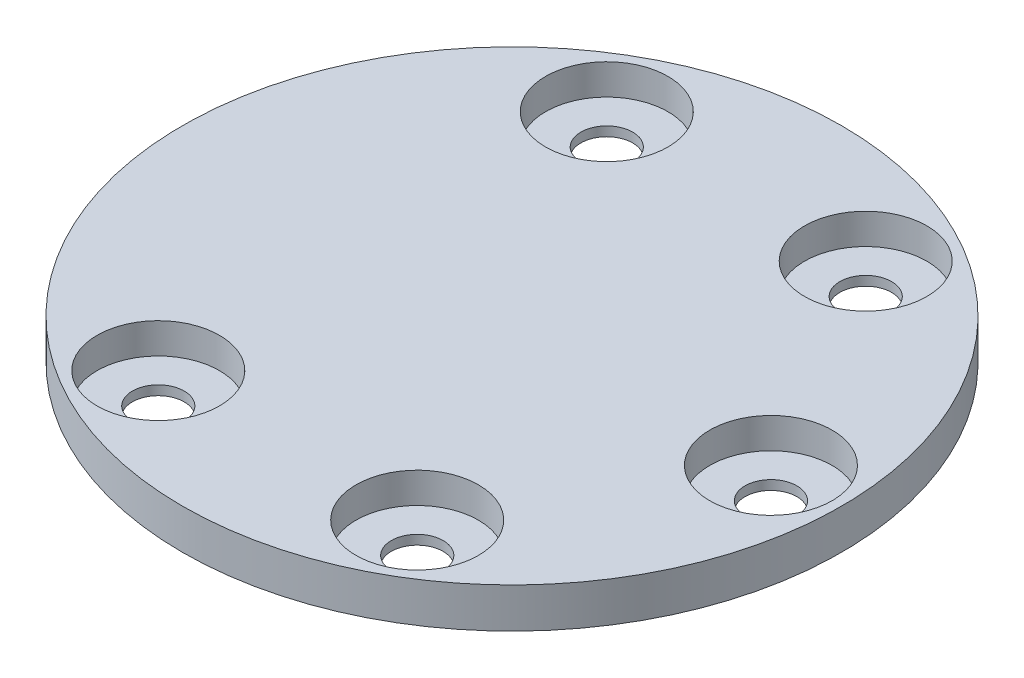
SolidWorks part; units mm, degrees
material "1060 Alloy"
ref_plane "Front Plane" through (0, 0, 0) normal (0, 0, 1) x (1, 0, 0)
ref_plane "Top Plane" through (0, 0, 0) normal (0, 1, 0) x (1, 0, 0)
ref_plane "Right Plane" through (0, 0, 0) normal (1, 0, 0) x (0, 0, -1)
sketch "Sketch1" plane through (0, 0, 0) normal (0, 1, 0) x (1, 0, 0)
  circle A0 centre (0, 0) radius 14
  dimension "D1" = 28
extrude "Boss-Extrude1" add sketch "Sketch1" along normal blind 1.7
sketch "Sketch3" plane through (0, 1.7, 0) normal (0, 1, 0) x (1, 0, 0)
  circle A0 centre (0, -10.25) radius 0.25
  circle A1 centre (0, 0) radius 9.8
  dimension "D1" = 0.5
  dimension "D2" = 10.25
  dimension "D3" = 19.6
sketch "Sketch4" plane through (0, 1.7, 0) normal (0, -1, 0) x (1, 0, 0)
  line L0 (0, 0) -> (13.2597, 13.2597) construction
  circle A0 centre (7.7782, 7.7782) radius 1
  dimension "D2" = 2
  dimension "D1" = 11
sketch "Sketch5" plane through (0, 1.7, 0) normal (0, 1, 0) x (1, 0, 0)
  circle A0 centre (0, 0) radius 11
  dimension "D1" = 22
hole_wizard "CBORE for M5 Hex Head Bolt1" positions "Sketch6" profile "Sketch7" counterbore size "M5" standard "ISO"
sketch "Sketch6" plane through (0, 1.7, 0) normal (0, 1, 0) x (1, 0, 0)
  point P0 (11, 0)
  dimension "D1" = 11
sketch "Sketch7" plane through (11, 1.7, 0) normal (1, 0, 0) x (0, 0, 1)
  line L0 (0, 0) -> (0, 5.6609)
  line L1 (0, 5.6609) -> (1.1, 5)
  line L2 (1.1, 5) -> (1.1, 1.3)
  line L3 (1.1, 1.3) -> (2.6, 1.3)
  line L4 (2.6, 1.3) -> (2.6, 0)
  line L5 (2.6, 0) -> (0, 0)
  line L10 (0, 5.6609) -> (-1.1, 5) construction
  line L11 (0, -6.35) -> (0, 107.95) construction
  dimension "Hole Dia." = 2.2
  dimension "Hole Depth" = 5
  dimension "C'Bore Dia." = 5.2
  dimension "C'Bore Depth" = 1.3
  dimension "Drill Angle" = 118
pattern_circular "CirPattern1" count 6 over 360 about axis through (0, 1.7, 0) along (0, 1, 0) skipping 3 of "CBORE for M5 Hex Head Bolt1"
sketch "Sketch8" plane through (0, 0, 0) normal (0, -1, 0) x (1, 0, 0)
  line L1 (3.1, 0.4) -> (4.9, 0.4)
  line L2 (3.1, 0.4) -> (3.1, -0.4)
  line L3 (3.1, -0.4) -> (4.9, -0.4)
  line L4 (4.9, 0.4) -> (4.9, -0.4)
  dimension "D1" = 1.8
  dimension "D2" = 0.8
  dimension "D3" = 0.4
  dimension "D4" = 3.1
extrude "Boss-Extrude2" add sketch "Sketch8" along normal blind 1
fillet "Fillet1" radius 0.25 8 edges at (4.9, -0.5, 0.4) (3.1, -0.5, 0.4) (3.1, -0.5, -0.4) (4.9, -0.5, -0.4) (4, -1, 0.4) (4.9, -1, 0) (4, -1, -0.4) (3.1, -1, 0)
